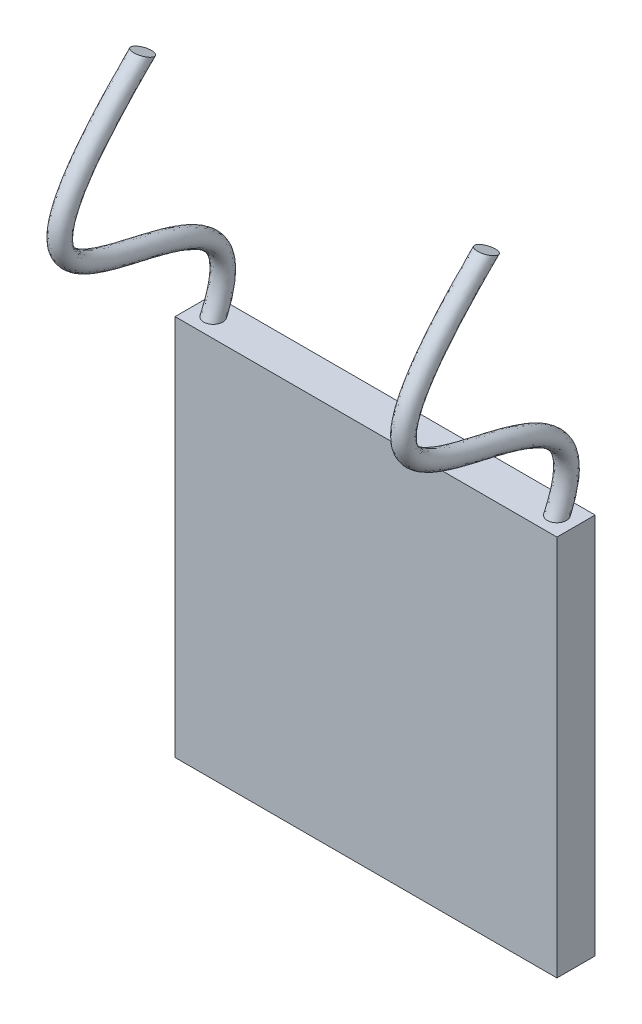
SolidWorks part; units mm, degrees
ref_plane "Front Plane" through (0, 0, 0) normal (0, 0, 1) x (1, 0, 0)
ref_plane "Top Plane" through (0, 0, 0) normal (0, 1, 0) x (1, 0, 0)
ref_plane "Right Plane" through (0, 0, 0) normal (1, 0, 0) x (0, 0, -1)
sketch "Sketch1" plane through (0, 0, 0) normal (0, 0, 1) x (1, 0, 0)
  line L1 (20, -20) -> (-20, -20)
  line L2 (20, -20) -> (20, 20)
  line L3 (20, 20) -> (-20, 20)
  line L4 (-20, -20) -> (-20, 20)
  line L5 (20, -20) -> (-20, 20) construction
  line L6 (20, 20) -> (-20, -20) construction
  point P0 (0, 0)
  dimension "D1" = 40
  dimension "D2" = 40
extrude "Boss-Extrude1" add sketch "Sketch1" along normal blind 4
sketch "Sketch2" plane through (-20, 0, 0) normal (-1, 0, 0) x (0, 0, 1)
  line L0 (4, 20) -> (0, 20) construction
  spline S0 degree 3 poles (2, 20) (-5.7462, 37.0736) (35.271, 22.2286) (9.3927, 47.7315) knots 0 0 0 0 1 1 1 1
  point P2 (9.3927, 47.7315)
  point P4 (13.1809, 30.8952)
  point P6 (2, 26.6861)
sketch "Sketch3" plane through (0, 20, 0) normal (0, 1, 0) x (1, 0, 0)
  line L0 (-20, -4) -> (-20, 0) construction
  line L1 (20, -4) -> (20, 0) construction
  circle A0 centre (-18, -2) radius 1
  circle A1 centre (18, -2) radius 1
  point P9 (20, -2)
  dimension "D1" = 2
  dimension "D2" = 2
  dimension "D3" = 2
  dimension "D4" = 2
sweep "Sweep1" add profiles "Sketch3" path "Sketch2"
